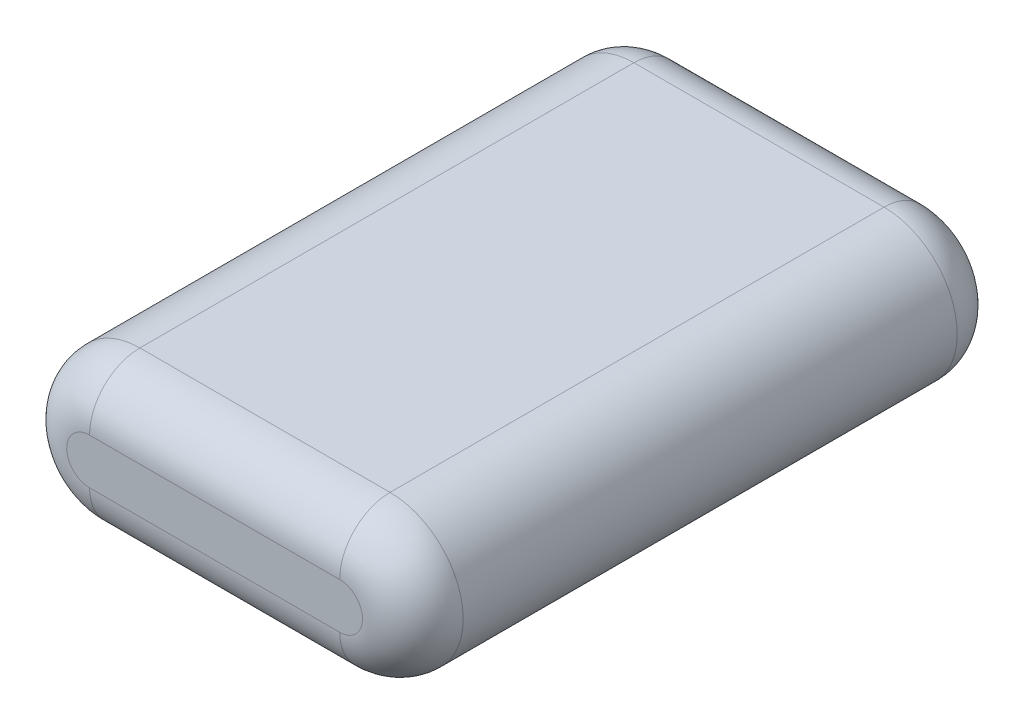
SolidWorks part; units mm, degrees
ref_plane "Front Plane" through (0, 0, 0) normal (0, 0, 1) x (1, 0, 0)
ref_plane "Top Plane" through (0, 0, 0) normal (0, 1, 0) x (1, 0, 0)
ref_plane "Right Plane" through (0, 0, 0) normal (1, 0, 0) x (0, 0, -1)
sketch "Sketch1" plane through (0, 0, 0) normal (0, 0, 1) x (1, 0, 0)
  line L0 (0, -23.7961) -> (0, 23.7961) construction
  line L1 (0, 0) -> (-55.5503, 0) construction
  line L2 (19.875, 11.625) -> (-19.875, 11.625)
  line L3 (-19.875, 0) -> (-31.5, 0) construction
  line L4 (19.875, -11.625) -> (-19.875, -11.625)
  line L5 (31.5, 0) -> (31.5, 10.2058) construction
  line L6 (-31.5, 0) -> (-31.5, 8.6848) construction
  arc A0 (-19.875, 11.625) -> (-19.875, -11.625) centre (-19.875, 0) ccw
  arc A1 (19.875, 11.625) -> (19.875, -11.625) centre (19.875, 0) cw
  point P4 (0, 0)
  point P13 (0, -11.625)
  point P15 (0, 11.625)
  point P21 (-31.5, 0)
  dimension "D1" = 23.25
  dimension "D2" = 63
extrude "Boss-Extrude1" add sketch "Sketch1" along normal blind 94.5
sketch "Sketch2" plane through (0, 0, 0) normal (0, 0, -1) x (-1, 0, 0)
  line L0 (0, -11.625) -> (0, 11.625) construction
  line L1 (-19.875, 11.625) -> (19.875, 11.625) construction
  line L2 (0, 0) -> (-31.5, 0) construction
  line L3 (20.45, 6.05) -> (-20.45, 6.05)
  line L4 (20.45, -6.05) -> (-20.45, -6.05)
  line L5 (-26.5, 0) -> (-26.5, 4.0163) construction
  arc A0 (-19.875, 11.625) -> (-19.875, -11.625) centre (-19.875, 0) ccw construction
  arc A1 (-20.45, 6.05) -> (-20.45, -6.05) centre (-20.45, 0) ccw
  arc A2 (20.45, 6.05) -> (20.45, -6.05) centre (20.45, 0) cw
  point P6 (0, 0)
  point P20 (0, -6.05)
  point P21 (0, 6.05)
  dimension "D1" = 12.1
  dimension "D2" = 53
extrude "Cut-Extrude1" cut sketch "Sketch2" against normal blind 1
chamfer "Chamfer3" distance 1.5 angle 35 4 edges at (-26.5, 0, 0) (0, 6.05, 0) (0, -6.05, 0) (26.5, 0, 0) first distance on face at (0, 0, 0)
sketch "Sketch3" plane through (0, 0, 1) normal (0, 0, -1) x (-1, 0, 0)
  line L0 (26.5719, 0) -> (-26.5719, 0) construction
  line L1 (0, 0) -> (0, -2.675) construction
  line L2 (-23.5719, -2.675) -> (-10.7719, -2.675)
  line L3 (-23.5719, -2.675) -> (-23.5719, 2.675)
  line L4 (-23.5719, 2.675) -> (-10.7719, 2.675)
  line L5 (-10.7719, -2.675) -> (-10.7719, 2.675)
  line L6 (-23.5719, -2.675) -> (-10.7719, 2.675) construction
  line L7 (-23.5719, 2.675) -> (-10.7719, -2.675) construction
  line L9 (23.5719, 2.675) -> (10.7719, 2.675)
  line L10 (10.7719, -2.675) -> (10.7719, 2.675)
  line L11 (23.5719, -2.675) -> (10.7719, -2.675)
  line L12 (23.5719, -2.675) -> (23.5719, 2.675)
  line L13 (0, 0) -> (0, 6.1219) construction
  line L14 (20.45, 6.1219) -> (-20.45, 6.1219) construction
  line L15 (-2.85, 3.0609) -> (2.85, 3.0609) construction
  line L16 (-2.85, 4.3859) -> (2.85, 4.3859)
  line L17 (-2.85, 1.7359) -> (2.85, 1.7359)
  line L18 (-4.175, 3.0609) -> (-4.175, 3.9351) construction
  line L19 (4.175, 3.0609) -> (4.175, 3.9351) construction
  line L20 (-10.7719, -2.675) -> (10.7719, -2.675) construction
  line L21 (-3.45, -2.675) -> (3.45, -2.675)
  line L22 (2.7, -0.825) -> (-2.7, -0.825)
  line L23 (-3.45, -2.675) -> (-3.45, -1.575)
  line L24 (-3.45, -1.575) -> (-2.7, -0.825)
  line L25 (3.45, -1.575) -> (2.7, -0.825)
  line L26 (3.45, -2.675) -> (3.45, -1.575)
  arc A0 (-20.45, 6.1219) -> (-20.45, -6.1219) centre (-20.45, 0) ccw construction
  arc A1 (-2.85, 4.3859) -> (-2.85, 1.7359) centre (-2.85, 3.0609) ccw
  arc A2 (2.85, 1.7359) -> (2.85, 4.3859) centre (2.85, 3.0609) ccw
  point P0 (-17.1719, 0)
  point P7 (0, 0)
  point P26 (0, 3.0609)
  point P37 (0, -2.675)
  point P42 (0, -0.825)
  dimension "D1" = 12.8
  dimension "D2" = 5.35
  dimension "D3" = 3
  dimension "D4" = 8.35
  dimension "D5" = 2.65
  dimension "D6" = 6.9
  dimension "D7" = 1.1
  dimension "D8" = 1.85
  dimension "D9" = 5.4
extrude "Cut-Extrude2" cut sketch "Sketch3" against normal blind 6 contours L2 L5 L4 L3 | L11 L12 L9 L10 region at (17.1719, 0, 1) region at (-17.1719, 0, 1)
extrude "Cut-Extrude3" cut sketch "Sketch3<3>" against normal blind 6 contours L21 L26 L25 L22 L24 L23 region at (0, -1.7811, 1)
sketch "Sketch3<3>" plane through (0, 0, 1) normal (0, 0, -1) x (-1, 0, 0) same geometry as "Sketch3"
extrude "Cut-Extrude4" cut sketch "Sketch3<4>" against normal blind 6 contours L17 A2 L16 A1 region at (0, 3.0609, 1)
sketch "Sketch3<4>" plane through (0, 0, 1) normal (0, 0, -1) x (-1, 0, 0) same geometry as "Sketch3"
fillet "Fillet1" radius 8 8 edges at (31.5, 0, 0) (0, -11.625, 0) (-31.5, 0, 0) (31.5, 0, 94.5) (0, -11.625, 94.5) (-31.5, 0, 94.5) (0, 11.625, 0) (0, 11.625, 94.5)
ref_plane "Plane1" through (31.5, 0, 0) normal (1, 0, 0) x (0, 0, -1)
ref_plane "Plane2" through (-31.5, 0, 0) normal (-1, 0, 0) x (0, 0, 1)
